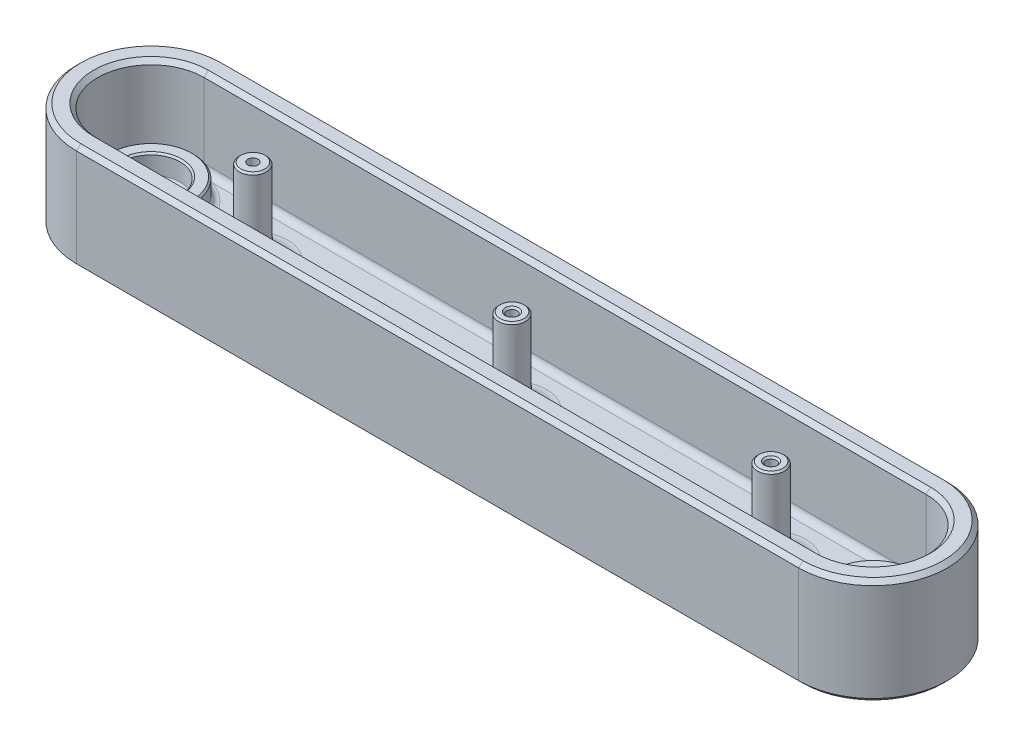
SolidWorks part; units mm, degrees
ref_plane "Front Plane" through (0, 0, 0) normal (0, 0, 1) x (1, 0, 0)
ref_plane "Top Plane" through (0, 0, 0) normal (0, 1, 0) x (1, 0, 0)
ref_plane "Right Plane" through (0, 0, 0) normal (1, 0, 0) x (0, 0, -1)
sketch "Sketch1" plane through (0, 0, 0) normal (0, 1, 0) x (1, 0, 0)
  line L0 (-107.95, 0) -> (107.95, 0) construction
  line L1 (0, -55.9739) -> (0, 55.9739) construction
  line L2 (-107.95, 22.225) -> (107.95, 22.225)
  line L3 (-107.95, -22.225) -> (107.95, -22.225)
  arc A0 (-107.95, 22.225) -> (-107.95, -22.225) centre (-107.95, 0) ccw
  arc A1 (107.95, 22.225) -> (107.95, -22.225) centre (107.95, 0) cw
  point P4 (0, 0)
  point P10 (0, 0)
  dimension "D2" = 44.45
  dimension "D1" = 215.9
extrude "MainBlock" add sketch "Sketch1" along normal blind 31.75
sketch "Sketch2" plane through (0, 31.75, 0) normal (0, 1, 0) x (1, 0, 0)
  line L0 (0, 0) -> (155.7407, 0) construction
  line L1 (0, 0) -> (0, 57.4416) construction
  line L2 (-107.95, -22.225) -> (107.95, -22.225) construction
  line L3 (107.95, 22.225) -> (-107.95, 22.225) construction
  line L4 (-107.95, -22.225) -> (107.95, -22.225) construction
  line L5 (107.95, 22.225) -> (-107.95, 22.225) construction
  line L6 (-107.95, 15.875) -> (107.95, 15.875)
  line L7 (-107.95, -15.875) -> (107.95, -15.875)
  arc A0 (107.95, -22.225) -> (107.95, 22.225) centre (107.95, 0) ccw construction
  arc A1 (-107.95, 22.225) -> (-107.95, -22.225) centre (-107.95, 0) ccw construction
  arc A2 (107.95, -22.225) -> (107.95, 22.225) centre (107.95, 0) ccw construction
  arc A3 (-107.95, 22.225) -> (-107.95, -22.225) centre (-107.95, 0) ccw construction
  arc A4 (-107.95, 15.875) -> (-107.95, -15.875) centre (-107.95, 0) ccw
  arc A5 (107.95, 15.875) -> (107.95, -15.875) centre (107.95, 0) cw
  point P18 (0, 15.875)
  point P19 (0, -15.875)
  dimension "D1" = 6.35
extrude "MainPocket" cut sketch "Sketch2" against normal blind 25.4
sketch "Sketch3" plane through (0, 0, 0) normal (0, -1, 0) x (1, 0, 0)
  line L2 (-107.95, -22.225) -> (107.95, -22.225)
  line L3 (107.95, 22.225) -> (-107.95, 22.225)
  line L4 (-107.95, -22.225) -> (107.95, -22.225) construction
  line L5 (107.95, 22.225) -> (-107.95, 22.225) construction
  circle A0 centre (-107.95, 0) radius 3.81
  circle A1 centre (107.95, 0) radius 3.81
  arc A2 (-107.95, 22.225) -> (-107.95, -22.225) centre (-107.95, 0) ccw
  arc A3 (107.95, -22.225) -> (107.95, 22.225) centre (107.95, 0) ccw
  arc A4 (-107.95, 22.225) -> (-107.95, -22.225) centre (-107.95, 0) ccw construction
  arc A5 (107.95, -22.225) -> (107.95, 22.225) centre (107.95, 0) ccw construction
  dimension "D2" = 7.62
  dimension "D3" = 7.62
extrude "Cut-Extrude1" cut sketch "Sketch3" against normal through all
sketch "Sketch4" plane through (0, 6.35, 0) normal (0, 1, 0) x (1, 0, 0)
  line L0 (0, 0) -> (50000, 0) construction
  line L1 (0, 0) -> (0, 50000) construction
  line L2 (107.95, 15.875) -> (-107.95, 15.875)
  line L3 (-107.95, -15.875) -> (107.95, -15.875)
  line L4 (107.95, 15.875) -> (-107.95, 15.875) construction
  line L5 (-107.95, -15.875) -> (107.95, -15.875) construction
  circle A0 centre (-107.95, 0) radius 8.7313
  circle A1 centre (-107.95, 0) radius 12.7
  arc A2 (107.95, -15.875) -> (107.95, 15.875) centre (107.95, 0) ccw
  arc A3 (-107.95, 15.875) -> (-107.95, -15.875) centre (-107.95, 0) ccw
  arc A4 (107.95, -15.875) -> (107.95, 15.875) centre (107.95, 0) ccw construction
  arc A5 (-107.95, 15.875) -> (-107.95, -15.875) centre (-107.95, 0) ccw construction
  circle A6 centre (107.95, 0) radius 12.7
  circle A7 centre (107.95, 0) radius 8.7313
  dimension "D2" = 17.4625
  dimension "D3" = 25.4
  dimension "D1" = 0
extrude "Boss-Extrude1" add sketch "Sketch4" along normal blind 6.35
sketch "Sketch5" plane through (0, 0, 0) normal (0, -1, 0) x (1, 0, 0)
  line L0 (0, 0) -> (0, 50000) construction
  line L2 (-107.95, -22.225) -> (107.95, -22.225)
  line L3 (107.95, 22.225) -> (-107.95, 22.225)
  line L4 (-107.95, -22.225) -> (107.95, -22.225) construction
  line L5 (107.95, 22.225) -> (-107.95, 22.225) construction
  circle A0 centre (-107.95, 0) radius 6.35
  circle A1 centre (-107.95, 0) radius 3.81 construction
  arc A2 (-107.95, 22.225) -> (-107.95, -22.225) centre (-107.95, 0) ccw
  arc A3 (107.95, -22.225) -> (107.95, 22.225) centre (107.95, 0) ccw
  arc A4 (-107.95, 22.225) -> (-107.95, -22.225) centre (-107.95, 0) ccw construction
  arc A5 (107.95, -22.225) -> (107.95, 22.225) centre (107.95, 0) ccw construction
  circle A6 centre (-107.95, 0) radius 3.81
  circle A7 centre (107.95, 0) radius 3.81 construction
  circle A8 centre (107.95, 0) radius 6.35 construction
  dimension "D2" = 12.7
  dimension "D1" = 0
extrude "Boss-Extrude2" [suppressed] add sketch "Sketch5" along normal blind 3.81
fillet "Fillet1" [suppressed] radius 1.27
sketch "Sketch7" plane through (0, 6.35, 0) normal (0, 1, 0) x (1, 0, 0)
  line L0 (1.3556, 0) -> (50001.3556, 0) construction
  circle A0 centre (0, 0) radius 1.524
  circle A1 centre (-77.47, 0) radius 1.524
  circle A2 centre (-107.95, 0) radius 3.81 construction
  circle A3 centre (107.95, 0) radius 3.81 construction
  circle A4 centre (107.95, 0) radius 3.81 construction
  circle A5 centre (-107.95, 0) radius 3.81 construction
  circle A6 centre (77.47, 0) radius 1.524
  circle A7 centre (-77.47, 0) radius 4.064
  circle A8 centre (0, 0) radius 4.064
  circle A9 centre (77.47, 0) radius 4.064
  dimension "D3" = 3.048
  dimension "D4" = 3.048
  dimension "D5" = 3.048
  dimension "D6" = 8.128
  dimension "D7" = 8.128
  dimension "D8" = 8.128
  dimension "D1" = 30.48
  dimension "D2" = 30.48
extrude "Boss-Extrude3" add sketch "Sketch7" along normal up to surface (25.4 mm away) up to face at (0, 31.75, 0)
fillet "Fillet2" radius 0.635 2 edges at (107.95, 6.35, -8.7313) (-107.95, 6.35, 8.7313)
fillet "Fillet3" radius 1.905 6 edges at (123.825, 6.35, 0) (0, 6.35, 15.875) (-123.825, 6.35, 0) (107.95, 6.35, -12.7) (-107.95, 6.35, -12.7) (0, 6.35, -15.875)
fillet "Fillet6" radius 6.35 3 edges at (77.47, 6.35, -4.064) (0, 6.35, -4.064) (-77.47, 6.35, -4.064)
sketch "Sketch9" plane through (0, 0, 0) normal (0, -1, 0) x (1, 0, 0)
  circle A0 centre (107.95, 0) radius 3.81 construction
  circle A1 centre (107.95, 0) radius 3.81
  circle A6 centre (107.95, 0) radius 6.35
  dimension "D2" = 12.7
extrude "Boss-Extrude4" add sketch "Sketch9" along normal blind 6.35
fillet "Fillet7" radius 1.27 1 edges at (107.95, 0, 6.35)
chamfer "Chamfer1" [suppressed] distance 0.508 angle 45
chamfer "Chamfer2" distance 0.508 angle 45 11 edges at (77.47, 31.75, 1.524) (107.95, 6.35, -3.81) (107.95, 12.7, -12.7) (107.95, 12.7, -8.7313) (-107.95, 6.35, -3.81) (-107.95, 12.7, 12.7) (-77.47, 31.75, 4.064) (0, 31.75, 4.064) (0, 31.75, 1.524) (77.47, 31.75, 4.064) (-107.95, 12.7, 8.7313)
chamfer "Chamfer3" distance 1.27 angle 45 8 edges at (0, 31.75, -22.225) (-130.175, 31.75, 0) (130.175, 31.75, 0) (0, 31.75, 22.225) (0, 31.75, -15.875) (-123.825, 31.75, 0) (123.825, 31.75, 0) (0, 31.75, 15.875)
chamfer "Chamfer4" distance 1.27 angle 45 4 edges at (0, 0, -22.225) (-130.175, 0, 0) (130.175, 0, 0) (0, 0, 22.225)
equation "\"D3@Sketch3\"=\"D2@Sketch3\""
equation "\"D5@Sketch7\"=\"D3@Sketch7\""
equation "\"D4@Sketch7\"=\"D3@Sketch7\""
equation "\"D7@Sketch7\"=\"D6@Sketch7\""
equation "\"D8@Sketch7\"=\"D6@Sketch7\""
